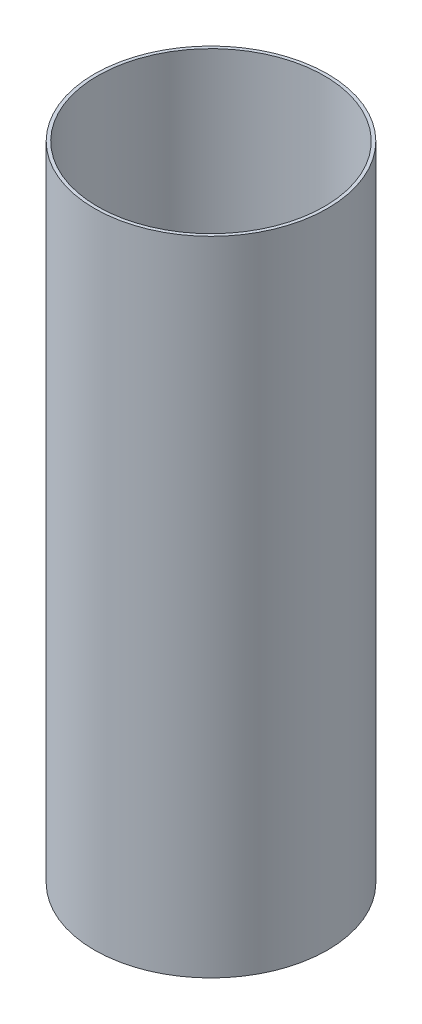
SolidWorks part; units mm, degrees
material "Acrylic (Medium-high impact)"
ref_plane "Front Plane" through (0, 0, 0) normal (0, 0, 1) x (1, 0, 0)
ref_plane "Top Plane" through (0, 0, 0) normal (0, 1, 0) x (1, 0, 0)
ref_plane "Right Plane" through (0, 0, 0) normal (1, 0, 0) x (0, 0, -1)
sketch "Sketch1" plane through (0, 0, 0) normal (0, 1, 0) x (1, 0, 0)
  circle A0 centre (0, 0) radius 76.2
  circle A1 centre (0, 0) radius 78.359
  dimension "D1" = 152.4
  dimension "D2" = 156.718
extrude "Boss-Extrude1" add sketch "Sketch1" along normal blind 431.8
